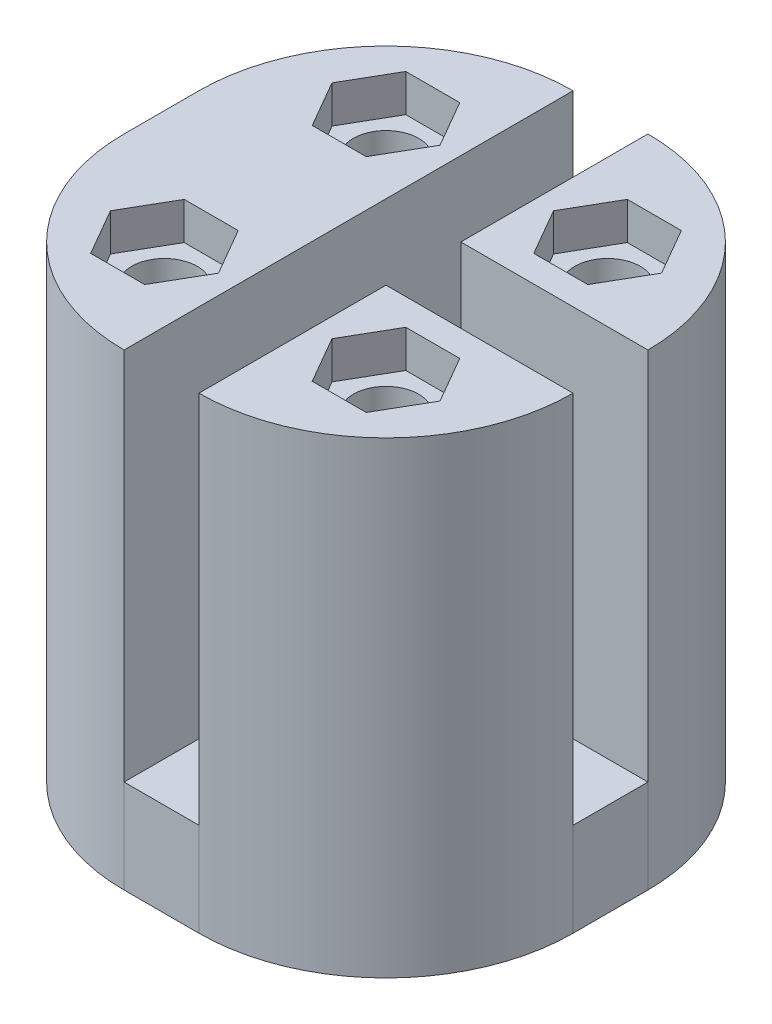
SolidWorks part; units mm, degrees
ref_plane "Front Plane" through (0, 0, 0) normal (0, 0, 1) x (1, 0, 0)
ref_plane "Top Plane" through (0, 0, 0) normal (0, 1, 0) x (1, 0, 0)
ref_plane "Right Plane" through (0, 0, 0) normal (1, 0, 0) x (0, 0, -1)
sketch "Sketch1" plane through (0, 0, 0) normal (0, 1, 0) x (1, 0, 0)
  line L0 (0, 15.136) -> (0, -8.864)
  line L1 (4, 15.136) -> (4, 5.136)
  line L2 (4, 5.136) -> (14, 5.136)
  line L3 (4, 1.136) -> (4, -8.864)
  line L4 (4, 1.136) -> (14, 1.136)
  line L5 (0, 15.136) -> (-10, 15.136)
  line L6 (-10, 15.136) -> (-10, -8.864)
  line L7 (-10, -8.864) -> (0, -8.864)
  arc A0 (4, 15.136) -> (14, 5.136) centre (4, 5.136) cw
  arc A1 (14, 1.136) -> (4, -8.864) centre (4, 1.136) cw
  dimension "D1" = 4
  dimension "D2" = 4
  dimension "D3" = 24
  dimension "D4" = 10
  dimension "D5" = 10
  dimension "D6" = 0
  dimension "D7" = 10
  dimension "D8" = 10
  dimension "D9" = 10
extrude "Boss-Extrude1" add sketch "Sketch1" along normal blind 20 contours L6 L7 L0 L5 | A1 L4 L3 | A0 L1 L2 region at (-5, 0, -3.136) region at (8.2441, 0, -9.3801) region at (8.2441, 0, 3.1081)
sketch "Sketch2" plane through (0, 0, 0) normal (0, -1, 0) x (1, 0, 0)
  line L0 (-10, 8.864) -> (-10, -15.136) construction
  line L1 (-10, -15.136) -> (0, -15.136) construction
  line L3 (0, 8.864) -> (-10, 8.864) construction
  line L8 (-10, 8.864) -> (-10, -15.136)
  line L9 (-10, -15.136) -> (0, -15.136)
  line L11 (0, 8.864) -> (-10, 8.864)
  line L16 (0, -15.136) -> (4, -15.136)
  line L17 (14, -5.136) -> (14, -1.136)
  line L18 (4, 8.864) -> (0, 8.864)
  arc A0 (14, -1.136) -> (4, 8.864) centre (4, -1.136) ccw construction
  arc A1 (4, -15.136) -> (14, -5.136) centre (4, -5.136) ccw construction
  arc A2 (14, -1.136) -> (4, 8.864) centre (4, -1.136) ccw
  arc A3 (4, -15.136) -> (14, -5.136) centre (4, -5.136) ccw
extrude "Boss-Extrude2" add sketch "Sketch2" along normal blind 5
fillet "Fillet1" radius 10 2 edges at (-10, 7.5, 8.864) (-10, 7.5, -15.136)
sketch "Sketch3" plane through (0, 20, 0) normal (0, 1, 0) x (1, 0, 0)
  line L0 (4, 5.136) -> (11.0711, 12.2071) construction
  arc A0 (14, 5.136) -> (4, 15.136) centre (4, 5.136) ccw construction
  circle A1 centre (7.9209, 9.0569) radius 1.75
  dimension "D1" = 3.5
extrude "Cut-Extrude1" cut sketch "Sketch3" against normal blind 29
ref_plane "Plane1" through (2, 0, 0) normal (1, 0, 0) x (0, 0, -1)
ref_plane "Plane2" through (0, 0, -3.136) normal (0, 0, 1) x (1, 0, 0)
mirror "Mirror1" about plane through (0, 0, -3.136) normal (0, 0, 1) of "Cut-Extrude1"
mirror "Mirror2" about plane through (2, 0, 0) normal (1, 0, 0) of "Mirror1"
sketch "Sketch4" plane through (0, 20, 0) normal (0, 1, 0) x (1, 0, 0)
  line L1 (10.8076, 9.0569) -> (9.3643, 11.5569)
  line L2 (9.3643, 11.5569) -> (6.4775, 11.5569)
  line L3 (6.4775, 11.5569) -> (5.0341, 9.0569)
  line L4 (5.0341, 9.0569) -> (6.4775, 6.5569)
  line L5 (6.4775, 6.5569) -> (9.3643, 6.5569)
  line L6 (9.3643, 6.5569) -> (10.8076, 9.0569)
  line L7 (10.8076, -2.7849) -> (9.3643, -0.2849)
  line L8 (9.3643, -0.2849) -> (6.4775, -0.2849)
  line L9 (6.4775, -0.2849) -> (5.0341, -2.7849)
  line L10 (5.0341, -2.7849) -> (6.4775, -5.2849)
  line L11 (6.4775, -5.2849) -> (9.3643, -5.2849)
  line L12 (9.3643, -5.2849) -> (10.8076, -2.7849)
  line L13 (-6.8076, -2.7849) -> (-5.3643, -5.2849)
  line L14 (-5.3643, -5.2849) -> (-2.4775, -5.2849)
  line L15 (-2.4775, -5.2849) -> (-1.0341, -2.7849)
  line L16 (-1.0341, -2.7849) -> (-2.4775, -0.2849)
  line L17 (-2.4775, -0.2849) -> (-5.3643, -0.2849)
  line L18 (-5.3643, -0.2849) -> (-6.8076, -2.7849)
  line L19 (-6.8076, 9.0569) -> (-5.3643, 6.5569)
  line L20 (-5.3643, 6.5569) -> (-2.4775, 6.5569)
  line L21 (-2.4775, 6.5569) -> (-1.0341, 9.0569)
  line L22 (-1.0341, 9.0569) -> (-2.4775, 11.5569)
  line L23 (-2.4775, 11.5569) -> (-5.3643, 11.5569)
  line L24 (-5.3643, 11.5569) -> (-6.8076, 9.0569)
  circle A0 centre (7.9209, 9.0569) radius 2.5 construction
  circle A1 centre (7.9209, -2.7849) radius 2.5 construction
  circle A2 centre (-3.9209, -2.7849) radius 2.5 construction
  circle A3 centre (-3.9209, 9.0569) radius 2.5 construction
  dimension "D1" = 5
extrude "Cut-Extrude2" cut sketch "Sketch4" against normal blind 2
